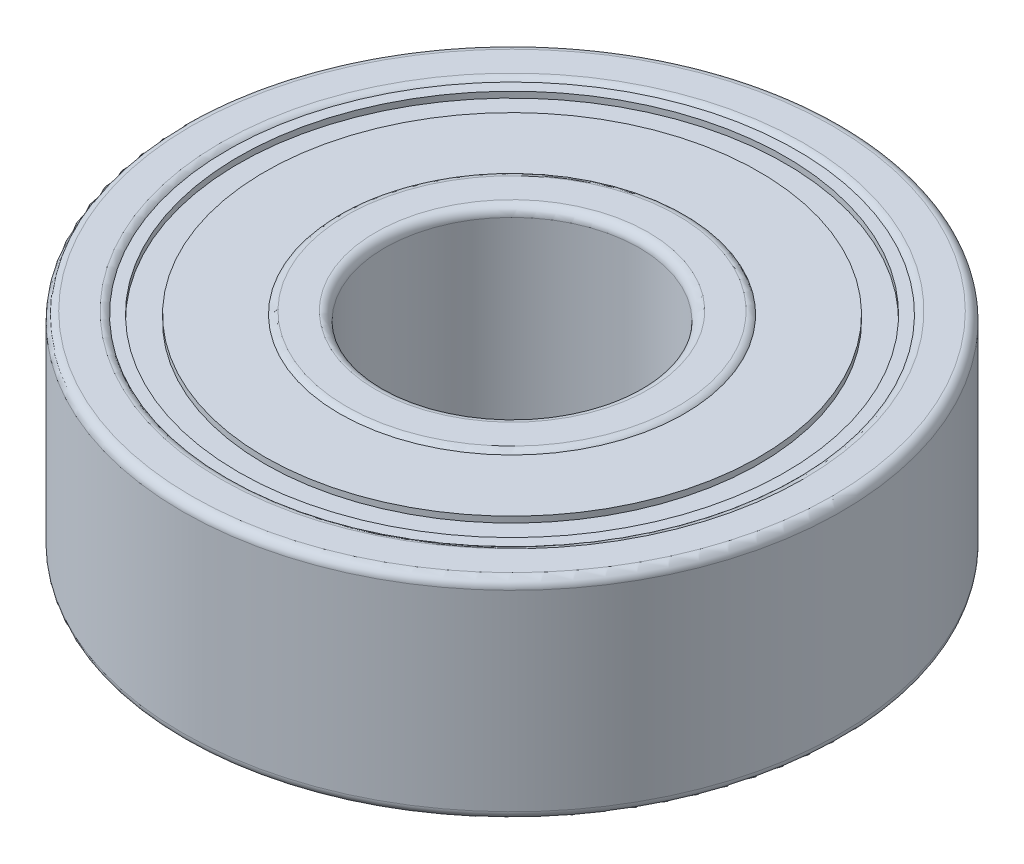
SolidWorks part; units mm, degrees
ref_plane "Front Plane" through (0, 0, 0) normal (0, 0, 1) x (1, 0, 0)
ref_plane "Top Plane" through (0, 0, 0) normal (0, 1, 0) x (1, 0, 0)
ref_plane "Right Plane" through (0, 0, 0) normal (1, 0, 0) x (0, 0, -1)
sketch "Sketch1" plane through (0, 0, 0) normal (0, 1, 0) x (1, 0, 0)
  circle A0 centre (0, 0) radius 4.25
  circle A1 centre (0, 0) radius 5.75
  dimension "D1" = 8.5
  dimension "D2" = 11.5
extrude "Boss-Extrude1" add sketch "Sketch1" along normal blind 7
sketch "Sketch2" plane through (0, 0, 0) normal (0, 1, 0) x (1, 0, 0)
  circle A0 centre (0, 0) radius 5.75
  circle A1 centre (0, 0) radius 9.5
  dimension "D1" = 11.5
  dimension "D2" = 19
extrude "Boss-Extrude2" add sketch "Sketch2" along normal blind 6.8 from offset 0.1
sketch "Sketch3" plane through (0, 6.9, 0) normal (0, 1, 0) x (1, 0, 0)
  circle A0 centre (0, 0) radius 8.25
  circle A1 centre (0, 0) radius 9.125
  dimension "D1" = 18.25
  dimension "D2" = 16.5
extrude "Cut-Extrude1" cut sketch "Sketch3" against normal blind 0.2
sketch "Sketch4" plane through (0, 0, 0) normal (0, 1, 0) x (1, 0, 0)
  circle A0 centre (0, 0) radius 9.5
  circle A1 centre (0, 0) radius 11
  dimension "D1" = 19
  dimension "D2" = 22
extrude "Boss-Extrude3" add sketch "Sketch4" along normal blind 7
fillet "Fillet1" radius 0.3 8 edges at (0, 0, 4.25) (0, 0, 5.75) (0, 0, 9.5) (0, 0, 11) (0, 7, 11) (0, 7, 9.5) (0, 7, 5.75) (0, 7, 4.25)
